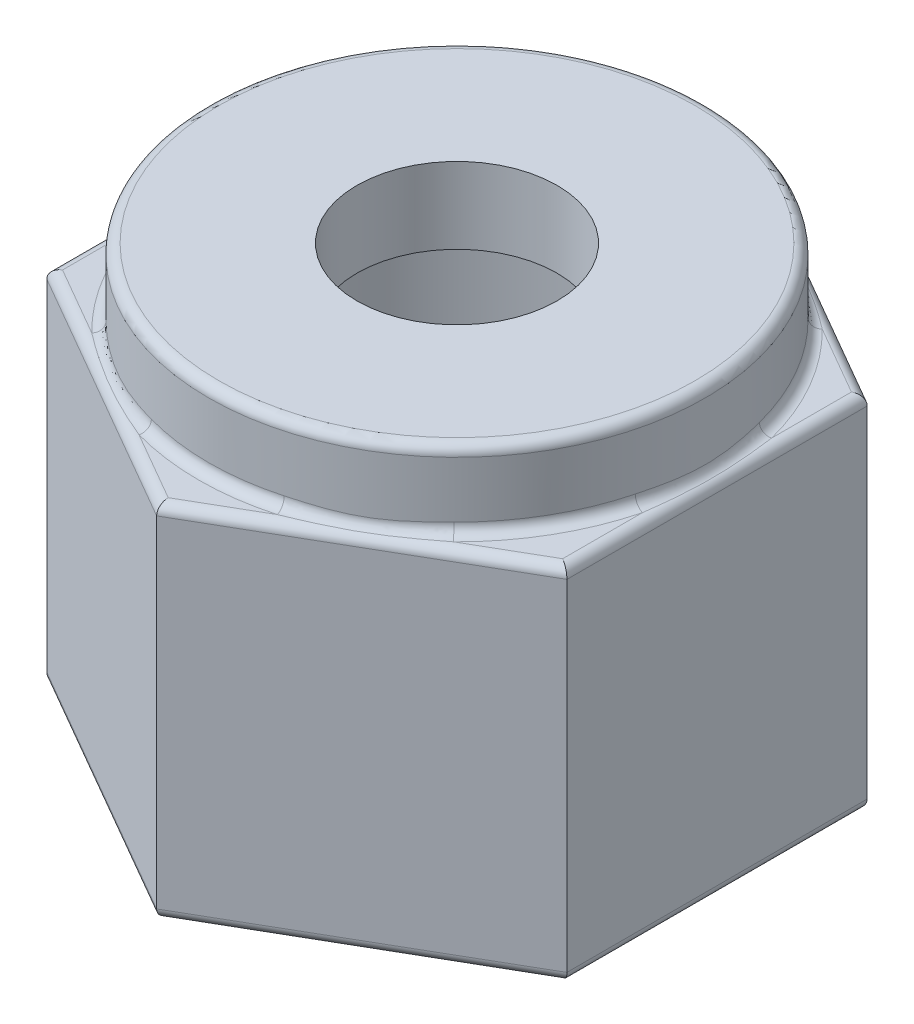
SolidWorks part; units mm, degrees
ref_plane "Спереди" through (0, 0, 0) normal (0, 0, 1) x (1, 0, 0)
ref_plane "Сверху" through (0, 0, 0) normal (0, 1, 0) x (1, 0, 0)
ref_plane "Справа" through (0, 0, 0) normal (1, 0, 0) x (0, 0, -1)
sketch "Эскиз1" plane through (0, 0, 0) normal (0, 1, 0) x (1, 0, 0)
  line L1 (0, 15) -> (-12.9904, 7.5)
  line L2 (-12.9904, 7.5) -> (-12.9904, -7.5)
  line L3 (-12.9904, -7.5) -> (0, -15)
  line L4 (0, -15) -> (12.9904, -7.5)
  line L5 (12.9904, -7.5) -> (12.9904, 7.5)
  line L6 (12.9904, 7.5) -> (0, 15)
  circle A0 centre (0, 0) radius 12.9904 construction
  dimension "D1" = 15
ref_plane "Плоскость1" through (0, -18, 0) normal (0, 1, 0) x (1, 0, 0)
sketch "Эскиз2" plane through (0, -18, 0) normal (0, 1, 0) x (1, 0, 0)
  line L0 (-12.9904, -7.5) -> (0, -15) construction
  line L1 (0, -15) -> (12.9904, -7.5) construction
  line L2 (12.9904, -7.5) -> (12.9904, 7.5) construction
  line L3 (12.9904, 7.5) -> (0, 15) construction
  line L4 (0, 15) -> (-12.9904, 7.5) construction
  line L5 (-12.9904, 7.5) -> (-12.9904, -7.5) construction
  line L6 (-12.9904, -7.5) -> (0, -15)
  line L7 (0, -15) -> (12.9904, -7.5)
  line L8 (12.9904, -7.5) -> (12.9904, 7.5)
  line L9 (12.9904, 7.5) -> (0, 15)
  line L10 (0, 15) -> (-12.9904, 7.5)
  line L11 (-12.9904, 7.5) -> (-12.9904, -7.5)
loft "По сечениям1" add profiles "Эскиз2", "Эскиз1" connector at (-12.9904, -18, -7.5) connector at (-12.9904, 0, -7.5)
sketch "Эскиз3" plane through (0, -18, 0) normal (0, -1, 0) x (1, 0, 0)
  circle A0 centre (0, 0) radius 10.188
  dimension "D1" = 20.376
extrude "Вырез-Вытянуть1" cut sketch "Эскиз3" against normal through all
cosmetic thread "Условное изображение резьбы1" parameters "D2"=22
sketch "Эскиз4" plane through (0, 0, 0) normal (0, 1, 0) x (1, 0, 0)
  circle A0 centre (0, 0) radius 12.4
  dimension "D1" = 24.8
ref_plane "Плоскость2" through (0, 3.8, 0) normal (0, 1, 0) x (1, 0, 0)
sketch "Эскиз5" plane through (0, 3.8, 0) normal (0, 1, 0) x (1, 0, 0)
  circle A0 centre (0, 0) radius 12.4 construction
  circle A1 centre (0, 0) radius 12.4
loft "По сечениям2" add profiles "Эскиз5", "Эскиз4" connector at (-0.5552, 3.8, 12.3876) connector at (0.5608, 0, 12.3873)
sketch "Эскиз6" plane through (0, 3.8, 0) normal (0, 1, 0) x (1, 0, 0)
  circle A0 centre (0, 0) radius 5
  dimension "D1" = 10
extrude "Вырез-Вытянуть2" cut sketch "Эскиз6" against normal through all
fillet "Скругление1" radius 0.5 1 edges at (0, 3.8, 12.4)
fillet "Скругление2" radius 0.5 12 edges
fillet "Скругление3" radius 0.5 1 edges at (0, 0, 12.4)
